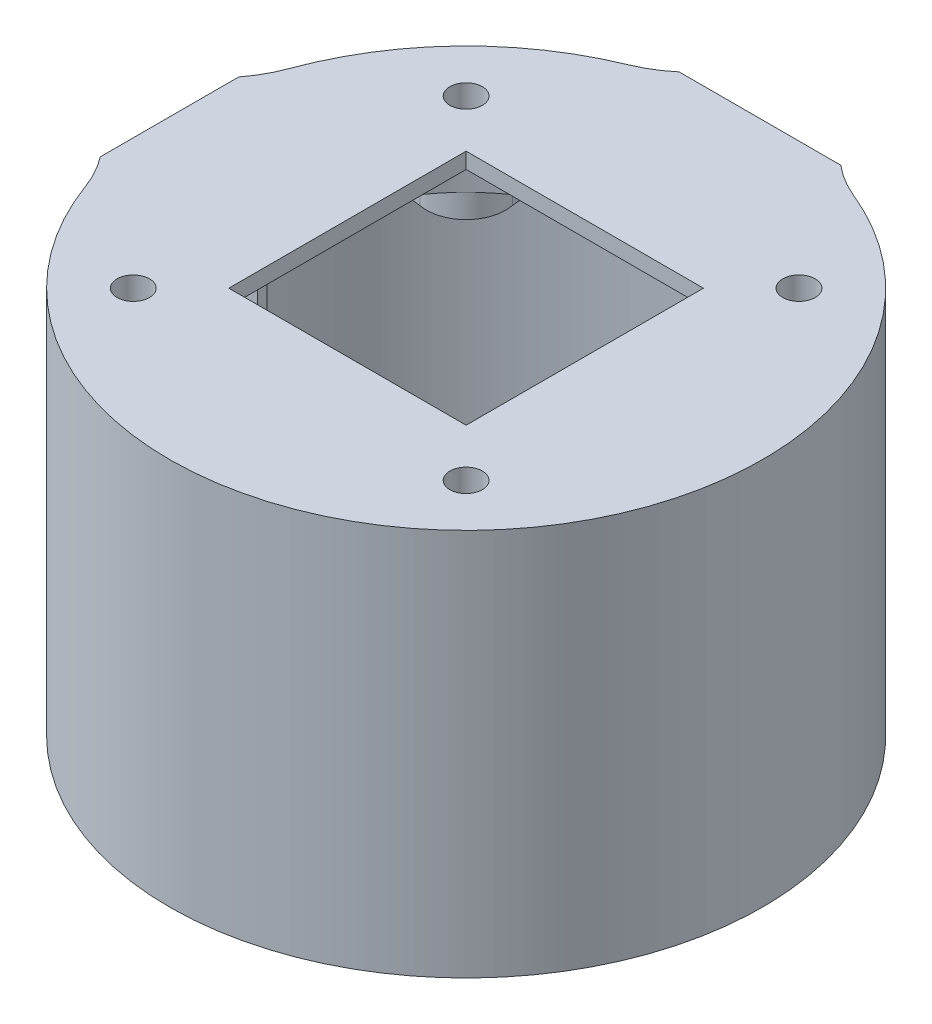
SolidWorks part; units mm, degrees
ref_plane "Спереди" through (0, 0, 0) normal (0, 0, 1) x (1, 0, 0)
ref_plane "Сверху" through (0, 0, 0) normal (0, 1, 0) x (1, 0, 0)
ref_plane "Справа" through (0, 0, 0) normal (1, 0, 0) x (0, 0, -1)
sketch "Sketch1" plane through (0, 0, 0) normal (0, 1, 0) x (1, 0, 0)
  circle A0 centre (0, 0) radius 70
  circle A1 centre (0, 0) radius 75
  dimension "D1" = 140
  dimension "D2" = 150
extrude "Boss-Extrude1" add sketch "Sketch1" along normal blind 78
sketch "Sketch2" plane through (0, 78, 0) normal (0, 1, 0) x (1, 0, 0)
  circle A0 centre (0, 0) radius 75
  circle A1 centre (0, 0) radius 75 construction
extrude "Boss-Extrude2" add sketch "Sketch2" along normal blind 20
sketch "Sketch3" plane through (0, 98, 0) normal (0, 1, 0) x (1, 0, 0)
  line L1 (42.0729, 42.0729) -> (-42.0729, 42.0729) construction
  line L2 (42.0729, 42.0729) -> (42.0729, -42.0729) construction
  line L3 (42.0729, -42.0729) -> (-42.0729, -42.0729) construction
  line L4 (-42.0729, 42.0729) -> (-42.0729, -42.0729) construction
  line L5 (42.0729, 42.0729) -> (-42.0729, -42.0729) construction
  line L6 (42.0729, -42.0729) -> (-42.0729, 42.0729) construction
  line L7 (22.5, 22.5) -> (-22.5, 22.5)
  line L8 (22.5, 22.5) -> (22.5, -22.5)
  line L9 (22.5, -22.5) -> (-22.5, -22.5)
  line L10 (-22.5, 22.5) -> (-22.5, -22.5)
  line L11 (22.5, 22.5) -> (-22.5, -22.5) construction
  line L12 (22.5, -22.5) -> (-22.5, 22.5) construction
  circle A0 centre (0, 0) radius 59.5 construction
  circle A1 centre (-42.0729, -42.0729) radius 4.1
  circle A2 centre (-42.0729, 42.0729) radius 4.1
  circle A3 centre (42.0729, 42.0729) radius 4.1
  circle A4 centre (42.0729, -42.0729) radius 4.1
  dimension "D1" = 119
  dimension "D2" = 8.2
  dimension "D3" = 45
extrude "Cut-Extrude1" cut sketch "Sketch3" against normal through all
sketch "Sketch5" plane through (0, 78, 0) normal (0, -1, 0) x (1, 0, 0)
  line L0 (0, 22.5) -> (0, 70) construction
  line L1 (-22.5, 22.5) -> (22.5, 22.5) construction
  line L3 (-22.5, 45.5) -> (22.5, 45.5)
  line L4 (-22.5, 45.5) -> (-22.5, 22.5)
  line L5 (-22.5, 22.5) -> (22.5, 22.5)
  line L6 (22.5, 45.5) -> (22.5, 22.5)
  line L7 (-22.5, 45.5) -> (22.5, 22.5) construction
  line L8 (-22.5, 22.5) -> (22.5, 45.5) construction
  circle A0 centre (0, 0) radius 70 construction
  point P7 (0, 34)
  dimension "D1" = 23
extrude "Cut-Extrude2" cut sketch "Sketch5" against normal blind 18
sketch "Sketch6" plane through (0, 78, 0) normal (0, -1, 0) x (1, 0, 0)
  circle A0 centre (0, 0) radius 61
  dimension "D1" = 122
extrude "Cut-Extrude3" cut sketch "Sketch6" against normal blind 6
sketch "Sketch7" plane through (0, 84, 0) normal (0, -1, 0) x (1, 0, 0)
  circle A0 centre (-42.0729, -42.0729) radius 10
  circle A1 centre (-42.0729, 42.0729) radius 10
  circle A2 centre (-42.0729, 42.0729) radius 4.1
  circle A3 centre (-42.0729, -42.0729) radius 4.1
  circle A4 centre (42.0729, -42.0729) radius 4.1
  circle A5 centre (42.0729, 42.0729) radius 4.1
  circle A6 centre (42.0729, -42.0729) radius 10
  circle A7 centre (42.0729, 42.0729) radius 10
  dimension "D1" = 20
extrude "Boss-Extrude3" add sketch "Sketch7" along normal up to surface (6 mm away) up to face at (0, 78, 0)
sketch "Sketch8" plane through (0, 84, 0) normal (0, -1, 0) x (1, 0, 0)
  circle A0 centre (0, 0) radius 49.5
  arc A1 (-49.6074, 35.4979) -> (-35.4979, 49.6074) centre (-42.0729, 42.0729) ccw construction
extrude "Cut-Extrude4" cut sketch "Sketch8" against normal blind 10
sketch "Sketch9" plane through (0, 0, 0) normal (0, -1, 0) x (1, 0, 0)
  line L0 (0, -75) -> (0, 75) construction
  line L1 (7.5, -74.6241) -> (-7.5, -74.6241)
  circle A0 centre (0, 0) radius 75 construction
  point P8 (0, -74.6241)
  dimension "D1" = 15
extrude "Cut-Extrude5" cut sketch "Sketch9" against normal through all and the other way through all
sketch "Sketch10" plane through (0, 0, -74.6241) normal (0, 0, -1) x (-1, 0, 0)
  line L0 (0, 0) -> (0, 98) construction
  line L1 (-7.5, 0) -> (7.5, 0) construction
  line L2 (-7.5, 98) -> (7.5, 98) construction
  line L4 (-7.5, 20.4) -> (7.5, 20.4)
  line L5 (-7.5, 20.4) -> (-7.5, 7.6)
  line L6 (-7.5, 7.6) -> (7.5, 7.6)
  line L7 (7.5, 20.4) -> (7.5, 7.6)
  line L8 (-7.5, 20.4) -> (7.5, 7.6) construction
  line L9 (-7.5, 7.6) -> (7.5, 20.4) construction
  point P6 (0, 14)
  dimension "D1" = 12.8
  dimension "D2" = 15
  dimension "D3" = 14
  dimension "D4" = 20.4
extrude "Cut-Extrude6" cut sketch "Sketch10" against normal blind 10
sketch "Sketch11" plane through (0, 0, -74.6241) normal (0, 0, -1) x (-1, 0, 0)
  line L0 (0, 20.4) -> (0, 7.6) construction
  line L1 (7.5, 20.4) -> (-7.5, 20.4) construction
  line L2 (-7.5, 7.6) -> (7.5, 7.6) construction
  line L4 (-10, 4) -> (10, 4)
  line L5 (-10, 4) -> (-10, 24)
  line L6 (-10, 24) -> (10, 24)
  line L7 (10, 4) -> (10, 24)
  line L8 (-10, 4) -> (10, 24) construction
  line L9 (-10, 24) -> (10, 4) construction
  point P6 (0, 14)
  dimension "D1" = 20
  dimension "D2" = 20
extrude "Cut-Extrude7" cut sketch "Sketch11" against normal blind 10 from offset 3 offset against normal yes
sketch "Sketch13" plane through (0, 78, 0) normal (0, -1, 0) x (1, 0, 0)
  line L0 (-70, 0) -> (61, 0) construction
  circle A0 centre (0, 0) radius 70 construction
  arc A1 (-49.6074, 35.4979) -> (-49.6074, -35.4979) centre (0, 0) ccw construction
  circle A2 centre (61, 0) radius 9
  dimension "D1" = 18
extrude "Cut-Extrude9" cut sketch "Sketch13" against normal up to surface (6 mm away) and the other way through all up to face at (0, 84, 45.599)
sketch "Sketch14" plane through (0, 0, 0) normal (0, -1, 0) x (1, 0, 0)
  line L0 (0, 0) -> (0, -110.0571) construction
  line L2 (10, -94.282) -> (-10, -94.282)
  line L3 (10, -94.282) -> (10, -69.282)
  line L4 (10, -69.282) -> (-10, -69.282) construction
  line L5 (-10, -94.282) -> (-10, -69.282)
  line L6 (10, -94.282) -> (-10, -69.282) construction
  line L7 (10, -69.282) -> (-10, -94.282) construction
  arc A0 (-10, -69.282) -> (10, -69.282) centre (0, 0) ccw construction
  circle A1 centre (0, 0) radius 70 construction
  arc A2 (10, -69.282) -> (-10, -69.282) centre (0, 0) cw
  point P6 (0, -70)
  point P7 (0, -81.782)
  dimension "D1" = 20
  dimension "D2" = 25
  dimension "D3" = 81.782
extrude "Boss-Extrude4" add sketch "Sketch14" against normal up to surface (98 mm away) up to face at (-42.0729, 98, -37.9729)
sketch "Sketch15" plane through (0, 0, 0) normal (0, -1, 0) x (1, 0, 0)
  line L0 (0, -59.1608) -> (0, -94.282) construction
  line L2 (-10, -94.282) -> (10, -94.282) construction
  line L4 (7.55, -91.5916) -> (-7.55, -91.5916)
  line L5 (7.55, -91.5916) -> (7.55, -69.5916)
  line L6 (7.55, -69.5916) -> (-7.55, -69.5916)
  line L7 (-7.55, -91.5916) -> (-7.55, -69.5916)
  line L8 (7.55, -91.5916) -> (-7.55, -69.5916) construction
  line L9 (7.55, -69.5916) -> (-7.55, -91.5916) construction
  circle A0 centre (0, 0) radius 70 construction
  point P6 (0, -80.5916)
  dimension "D1" = 15.1
  dimension "D2" = 22
extrude "Cut-Extrude10" cut sketch "Sketch15" against normal blind 20.4
fillet "Fillet1" radius 30 2 edges at (10, 49, -74.3303) (-10, 49, -74.3303)
sketch "Sketch16" plane through (0, 20.4, 0) normal (0, -1, 0) x (1, 0, 0)
  line L0 (0, -70) -> (0, -91.5916) construction
  line L1 (-7.55, -91.5916) -> (7.55, -91.5916) construction
  line L3 (7.55, -71.5916) -> (-7.55, -71.5916)
  line L4 (7.55, -71.5916) -> (7.55, -91.5916)
  line L5 (7.55, -91.5916) -> (-7.55, -91.5916)
  line L6 (-7.55, -71.5916) -> (-7.55, -91.5916)
  line L7 (7.55, -71.5916) -> (-7.55, -91.5916) construction
  line L8 (7.55, -91.5916) -> (-7.55, -71.5916) construction
  arc A0 (-7.55, -69.5916) -> (7.55, -69.5916) centre (0, 0) ccw construction
  point P7 (0, -81.5916)
  dimension "D1" = 20
extrude "Cut-Extrude11" cut sketch "Sketch16" against normal blind 2
sketch "Sketch17" plane through (0, 0, -91.5916) normal (0, 0, 1) x (1, 0, 0)
  line L0 (0, 22.4) -> (0, 0) construction
  line L1 (-7.55, 22.4) -> (7.55, 22.4) construction
  line L2 (-7.55, 0) -> (7.55, 0) construction
  line L4 (7.55, 9.6) -> (-7.55, 9.6)
  line L5 (7.55, 9.6) -> (7.55, 22.4)
  line L6 (7.55, 22.4) -> (-7.55, 22.4)
  line L7 (-7.55, 9.6) -> (-7.55, 22.4)
  line L8 (7.55, 9.6) -> (-7.55, 22.4) construction
  line L9 (7.55, 22.4) -> (-7.55, 9.6) construction
  point P6 (0, 16)
  dimension "D1" = 12.8
  dimension "D2" = 15.1
extrude "Cut-Extrude12" cut sketch "Sketch17" against normal through all
chamfer "Chamfer1" distance 20 angle 74 1 edges at (0, 98, -94.282) first distance on face at (0, 98, -44.4515)
sketch "Sketch20" plane through (0, 0, 0) normal (0, -1, 0) x (1, 0, 0)
  line L0 (0, 0) -> (-75, 0) construction
  line L2 (-65, -15) -> (-75, -15)
  line L3 (-65, -15) -> (-65, 15)
  line L4 (-65, 15) -> (-75, 15)
  line L5 (-75, -15) -> (-75, 15)
  line L6 (-65, -15) -> (-75, 15) construction
  line L7 (-65, 15) -> (-75, -15) construction
  arc A0 (28.4741, -69.3846) -> (-28.4741, -69.3846) centre (0, 0) ccw construction
  point P7 (-70, 0)
  point P17 (-75, 0)
  dimension "D1" = 10
  dimension "D2" = 30
extrude "Cut-Extrude13" cut sketch "Sketch20" against normal blind 30 from offset 20 offset against normal yes
sketch "Sketch21" plane through (0, 50, 0) normal (0, -1, 0) x (1, 0, 0)
  line L0 (-67.7772, 17.5) -> (-67.7772, -17.5)
  line L3 (-65.8886, 0) -> (-71.3886, 0) construction
  line L4 (-75, -17.5) -> (-67.7772, -17.5)
  line L5 (-75, -17.5) -> (-75, 17.5)
  line L6 (-75, 17.5) -> (-67.7772, 17.5)
  line L8 (-75, -17.5) -> (-67.7772, 17.5) construction
  line L9 (-75, 17.5) -> (-67.7772, -17.5) construction
  arc A1 (-73.4847, 15) -> (-73.4847, -15) centre (0, 0) ccw construction
  circle A3 centre (0, 0) radius 70 construction
  point P3 (-75, 0)
  point P12 (-71.3886, 0)
  dimension "D1" = 35
extrude "Boss-Extrude6" add sketch "Sketch21" along normal up to surface (50 mm away) and the other way up to surface (48 mm away) up to face at (0, 0, -45.6937) other way up to face at (0, 98, -35.5784)
sketch "Sketch22" plane through (-67.7772, 0, 0) normal (1, 0, 0) x (0, 0, -1)
  line L0 (0, 0) -> (0, 78) construction
  line L1 (-17.5, 0) -> (17.5, 0) construction
  line L2 (15, 78) -> (-15, 78)
  line L3 (-15, 78) -> (-15, 48)
  line L4 (17.5, 78) -> (-17.5, 78) construction
  line L5 (-15, 48) -> (15, 48)
  line L6 (15, 48) -> (15, 78)
  line L7 (17.5, 78) -> (-17.5, 78) construction
  point P12 (0, 78)
  dimension "D2" = 30
  dimension "D3" = 30
extrude "Cut-Extrude15" cut sketch "Sketch22" against normal through all
fillet "Fillet2" radius 30 2 edges at (-72.9298, 49, -17.5) (-72.9298, 49, 17.5)
sketch "Sketch23" plane through (0, 98, 0) normal (0, 1, 0) x (1, 0, 0)
  line L1 (-30, 30) -> (30, 30)
  line L2 (-30, 30) -> (-30, -30)
  line L3 (-30, -30) -> (30, -30)
  line L4 (30, 30) -> (30, -30)
  line L5 (-30, 30) -> (30, -30) construction
  line L6 (-30, -30) -> (30, 30) construction
  point P0 (0, 0)
  dimension "D1" = 60
  dimension "D2" = 60
extrude "Cut-Extrude16" cut sketch "Sketch23" against normal through all
sketch "Sketch25" plane through (0, 78, 0) normal (0, -1, 0) x (1, 0, 0)
  line L0 (0, 70) -> (0, -70) construction
  arc A0 (-67.7772, -17.5) -> (70, 0) centre (0, 0) ccw construction
  circle A1 centre (0, 61) radius 6
  arc A2 (35.4979, 49.6074) -> (-35.4979, 49.6074) centre (0, 0) ccw construction
  point P8 (0, 0)
  dimension "D1" = 12
extrude "Cut-Extrude17" cut sketch "Sketch25" against normal up to surface (6 mm away) up to face at (52.9037, 84, 0)
sketch "Sketch26" plane through (0, 78, 0) normal (0, -1, 0) x (1, 0, 0)
  circle A0 centre (-61, 0) radius 11
  arc A1 (-49.6074, 35.4979) -> (-49.6074, -35.4979) centre (0, 0) ccw construction
  dimension "D1" = 22
extrude "Cut-Extrude18" cut sketch "Sketch26" against normal up to surface (6 mm away) up to face at (0, 84, 48.015)
fillet "Fillet4" radius 10 8 edges at (49.6074, 81, 35.4979) (35.4979, 81, 49.6074) (49.6074, 81, -35.4979) (35.4979, 81, -49.6074) (-49.6074, 81, -35.4979) (-35.4979, 81, -49.6074) (-35.4979, 81, 49.6074) (-49.6074, 81, 35.4979)
